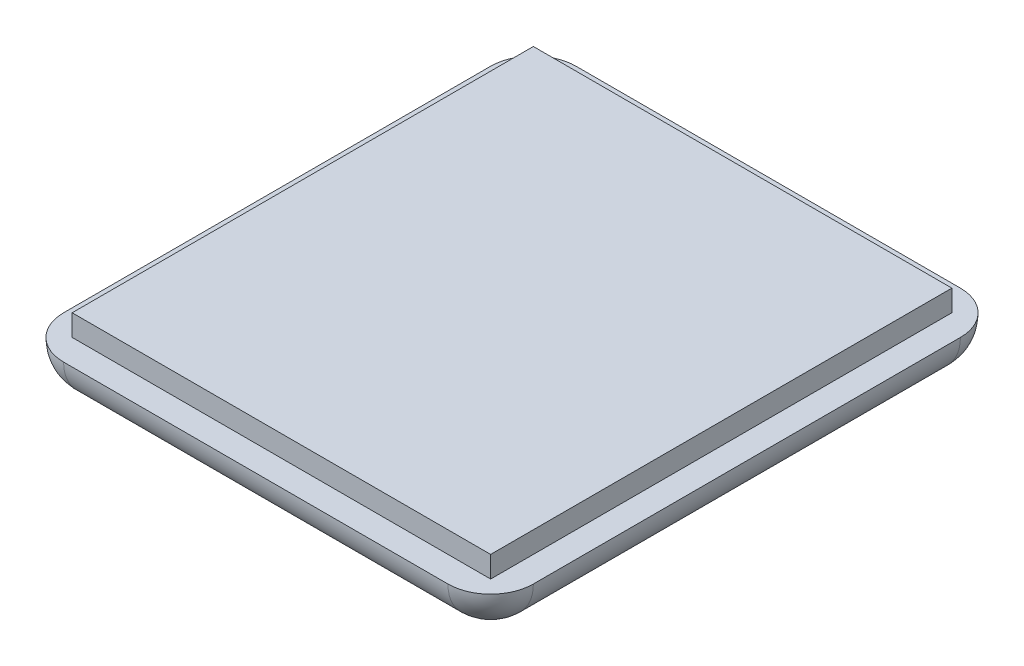
SolidWorks part; units mm, degrees
ref_plane "Front Plane" through (0, 0, 0) normal (0, 0, 1) x (1, 0, 0)
ref_plane "Top Plane" through (0, 0, 0) normal (0, 1, 0) x (1, 0, 0)
ref_plane "Right Plane" through (0, 0, 0) normal (1, 0, 0) x (0, 0, -1)
sketch "Sketch1" plane through (0, 0, 0) normal (0, 1, 0) x (1, 0, 0)
  line L0 (-24.5, 27) -> (24.5, -27) construction
  line L1 (-24.5, 27) -> (24.5, 27)
  line L2 (-24.5, 27) -> (-24.5, -27)
  line L3 (-24.5, -27) -> (24.5, -27)
  line L4 (24.5, 27) -> (24.5, -27)
  line L5 (24.5, 27) -> (-24.5, -27) construction
  point P4 (0, 0)
  dimension "D1" = 49
  dimension "D2" = 54
extrude "Boss-Extrude1" add sketch "Sketch1" along normal blind 2.5
sketch "Sketch2" plane through (0, 0, 0) normal (0, -1, 0) x (1, 0, 0)
  line L0 (-27.5, 30) -> (27.5, -30) construction
  line L1 (-27.5, 30) -> (27.5, 30)
  line L2 (-27.5, 30) -> (-27.5, -30)
  line L3 (-27.5, -30) -> (27.5, -30)
  line L4 (27.5, 30) -> (27.5, -30)
  line L5 (27.5, 30) -> (-27.5, -30) construction
  point P4 (0, 0)
  dimension "D1" = 60
  dimension "D2" = 55
extrude "Boss-Extrude2" add sketch "Sketch2" along normal blind 5
fillet "Fillet1" radius 5 4 edges at (-27.5, -5, 0) (0, -5, -30) (27.5, -5, 0) (0, -5, 30)
